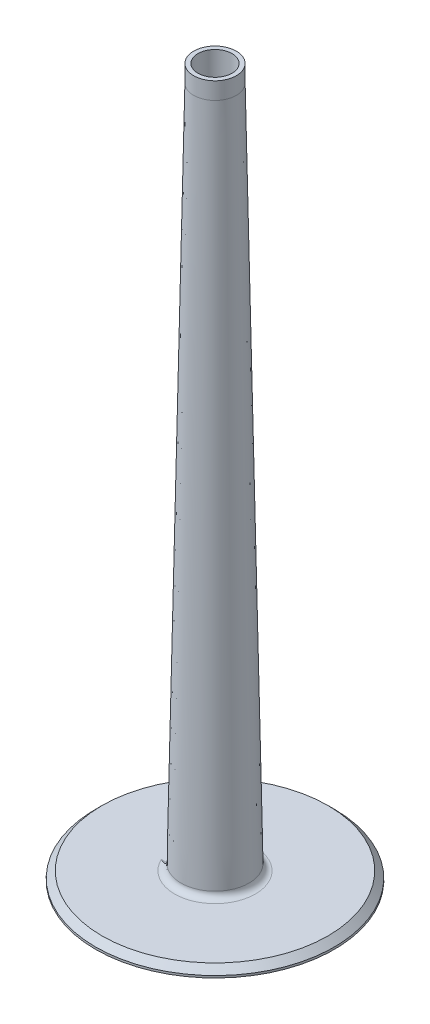
SolidWorks part; units mm, degrees
ref_plane "Front Plane" through (0, 0, 0) normal (0, 0, 1) x (1, 0, 0)
ref_plane "Top Plane" through (0, 0, 0) normal (0, 1, 0) x (1, 0, 0)
ref_plane "Right Plane" through (0, 0, 0) normal (1, 0, 0) x (0, 0, -1)
sketch "Sketch1" plane through (0, 0, 0) normal (1, 0, 0) x (0, 0, -1)
  line L0 (0, 254) -> (0, 0)
  line L1 (0, 0) -> (-12.7, 0)
  line L2 (-12.7, 0) -> (-7.9375, 254)
  line L3 (-7.9375, 254) -> (0, 254)
  dimension "D1" = 254
  dimension "D2" = 12.7
  dimension "D3" = 7.9375
revolve "Revolve1" add sketch "Sketch1" angle 360 about L0
sketch "Sketch3" plane through (0, 254, 0) normal (0, 1, 0) x (1, 0, 0)
  circle A0 centre (0, 0) radius 6.35
  dimension "D1" = 12.7
extrude "Cut-Extrude1" cut sketch "Sketch3" against normal through all
sketch "Sketch4" plane through (0, 0, 0) normal (0, -1, 0) x (1, 0, 0)
  circle A0 centre (0, 0) radius 44.45
  dimension "D1" = 88.9
extrude "Boss-Extrude1" add sketch "Sketch4" along normal blind 3.175
chamfer "Chamfer1" distance 2.38 angle 45 1 edges at (0, 0, -44.45)
sketch "Sketch6" plane through (0, 254, 0) normal (0, 1, 0) x (1, 0, 0)
  circle A0 centre (0, 0) radius 7.9375
  circle A1 centre (0, 0) radius 6.35
  circle A2 centre (0, 0) radius 6.35 construction
  circle A3 centre (0, 0) radius 7.9375 construction
extrude "Boss-Extrude3" add sketch "Sketch6" along normal blind 6.35
sketch "Sketch7" plane through (0, 0, 0) normal (1, 0, 0) x (0, 0, -1)
  line L0 (-6.35, 1.524) -> (6.35, 1.524) construction
  line L1 (-6.35, 3.048) -> (6.35, 3.048)
  line L2 (-6.35, 0) -> (6.35, 0)
  line L3 (42.07, 0) -> (-42.07, 0) construction
  arc A0 (-6.35, 3.048) -> (-6.35, 0) centre (-6.35, 1.524) ccw
  arc A1 (6.35, 0) -> (6.35, 3.048) centre (6.35, 1.524) ccw
  point P2 (0, 1.524)
  dimension "D1" = 12.7
  dimension "D2" = 1.524
extrude "Cut-Extrude2" cut sketch "Sketch7" against normal blind 16.51
fillet "Fillet1" radius 2.38 1 edges at (12.7, 0, 0)
